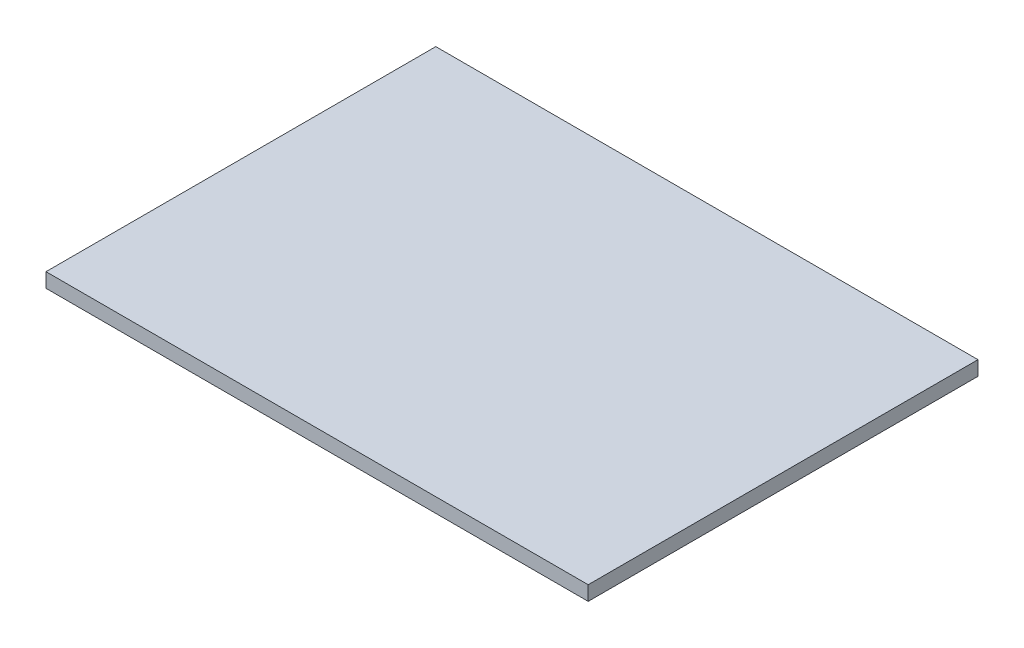
SolidWorks part; units mm, degrees
ref_plane "Front Plane" through (0, 0, 0) normal (0, 0, 1) x (1, 0, 0)
ref_plane "Top Plane" through (0, 0, 0) normal (0, 1, 0) x (1, 0, 0)
ref_plane "Right Plane" through (0, 0, 0) normal (1, 0, 0) x (0, 0, -1)
sketch "Sketch1" plane through (0, 0, 0) normal (0, 1, 0) x (1, 0, 0)
  line L1 (-169, -121.5) -> (169, -121.5)
  line L2 (-169, -121.5) -> (-169, 121.5)
  line L3 (-169, 121.5) -> (169, 121.5)
  line L4 (169, -121.5) -> (169, 121.5)
  line L5 (-169, -121.5) -> (169, 121.5) construction
  line L6 (-169, 121.5) -> (169, -121.5) construction
  point P0 (0, 0)
  dimension "D1" = 338
  dimension "D2" = 243
extrude "Boss-Extrude1" add sketch "Sketch1" along normal blind 9
equation "\"PCWidth\"= 172mm"
equation "\"PCLength\"= 320mm"
equation "\"PCHeight\"= 242mm"
equation "\"WallThickness\"= 9mm"
equation "\"ThermoBarrierThickness\"= 3mm"
equation "\"HotSideGap\"= 50mm"
equation "\"D1@Sketch1\"=\"PCLength\" + (2 * \"WallThickness\")"
equation "\"D2@Sketch1\"=\"PCWidth\" + \"ThermoBarrierThickness\" + \"HotSideGap\" + (2 * \"WallThickness\")"
equation "\"D1@Boss-Extrude1\"=\"WallThickness\""
equation "\"PCClearance\"= 25mm"
equation "\"RadiatorHeight\"= 275mm"
